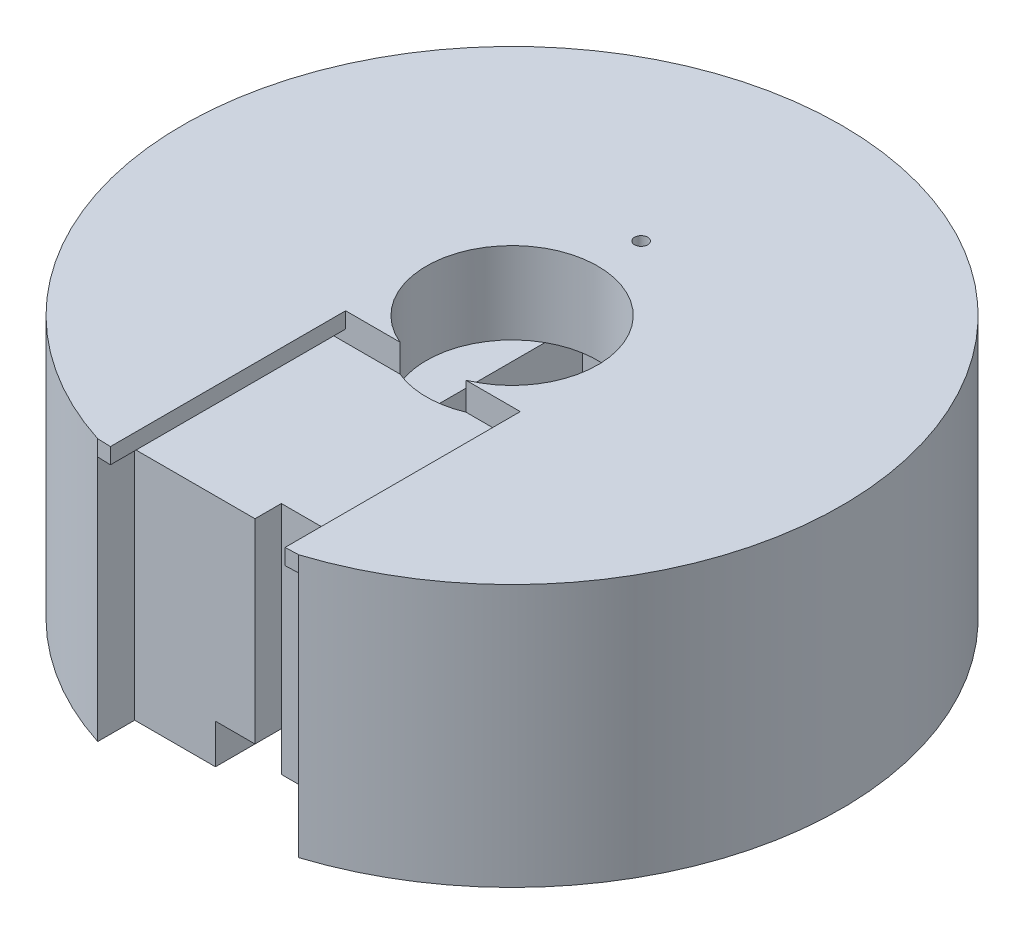
SolidWorks part; units mm, degrees
material "ABS"
ref_plane "Front Plane" through (0, 0, 0) normal (0, 0, 1) x (1, 0, 0)
ref_plane "Top Plane" through (0, 0, 0) normal (0, 1, 0) x (1, 0, 0)
ref_plane "Right Plane" through (0, 0, 0) normal (1, 0, 0) x (0, 0, -1)
ref_plane "Plane1" through (0, 0, -5.455) normal (0, 0, 1) x (1, 0, 0)
ref_axis "Axis1" through (0, 63.175, -5.455) along (0, -1, 0)
sketch "Sketch7" plane through (0, 0, 0) normal (0, 1, 0) x (1, 0, 0)
  line L0 (-6.35, 21.98) -> (-6.35, -11.07)
  line L1 (-5.95, 21.58) -> (5.95, 21.58) construction
  line L2 (-5.95, 21.58) -> (-5.95, -10.67) construction
  line L3 (-5.95, -10.67) -> (5.95, -10.67) construction
  line L4 (5.95, 21.58) -> (5.95, -10.67) construction
  line L5 (-5.95, 21.58) -> (5.95, -10.67) construction
  line L6 (-5.95, -10.67) -> (5.95, 21.58) construction
  line L7 (-6.35, -11.07) -> (6.35, -11.07)
  line L8 (6.35, 21.98) -> (6.35, -11.07)
  line L9 (-6.35, 21.98) -> (6.35, 21.98)
  circle A0 centre (0, 0) radius 50
  point P3 (0, 5.455)
  dimension "D1" = 100
  dimension "D2" = 11.9
  dimension "D3" = 32.25
  dimension "D4" = 0.4
extrude "Boss-Extrude4" add sketch "Sketch7" along normal blind 19.2
sketch "Sketch8" plane through (0, 19.2, 0) normal (0, 1, 0) x (1, 0, 0)
  line L0 (6.35, 21.98) -> (-6.35, 21.98) construction
  line L1 (-6.35, 17.055) -> (6.35, 17.055)
  line L2 (-6.35, 17.055) -> (-6.35, -6.145)
  line L3 (-6.35, -6.145) -> (6.35, -6.145)
  line L4 (6.35, 17.055) -> (6.35, -6.145)
  line L5 (-6.35, 17.055) -> (6.35, -6.145) construction
  line L6 (-6.35, -6.145) -> (6.35, 17.055) construction
  circle A0 centre (0, 0) radius 50
  circle A1 centre (0, 0) radius 50 construction
  point P0 (0, 5.455)
  dimension "D1" = 23.2
extrude "Boss-Extrude5" add sketch "Sketch8" along normal blind 8.2
sketch "Sketch11" plane through (0, 27.4, 0) normal (0, 1, 0) x (1, 0, 0)
  circle A0 centre (0, 0) radius 13
  circle A1 centre (0, 0) radius 50
  circle A2 centre (0, 0) radius 50 construction
  dimension "D1" = 26
extrude "Boss-Extrude6" add sketch "Sketch11" along normal blind 8.2
sketch "Sketch12" plane through (0, 19.2, 0) normal (0, -1, 0) x (1, 0, 0)
  line L0 (-6.35, 11.07) -> (6.35, 11.07) construction
  line L1 (6.35, -21.98) -> (-6.35, -21.98) construction
  circle A0 centre (0, 8.67) radius 1
  circle A1 centre (0, -19.58) radius 1
  dimension "D1" = 2.4
  dimension "D2" = 2
  dimension "D3" = 2.4
extrude "Cut-Extrude4" cut sketch "Sketch12" against normal through all
sketch "Sketch13" plane through (0, 0, 0) normal (0, -1, 0) x (1, 0, 0)
  line L1 (-15.25, 50) -> (15.25, 50)
  line L2 (-15.25, 50) -> (-15.25, 42)
  line L3 (-15.25, 42) -> (15.25, 42)
  line L4 (15.25, 50) -> (15.25, 42)
  circle A0 centre (0, 0) radius 50 construction
  point P6 (0, 42)
  dimension "D1" = 30.5
  dimension "D2" = 8
extrude "Cut-Extrude5" cut sketch "Sketch13" against normal up to surface (35.6 mm away) up to face at (0, 35.6, -20.58)
sketch "Sketch14" plane through (0, 0, 0) normal (0, -1, 0) x (1, 0, 0)
  line L0 (-6.35, 11.07) -> (6.35, 11.07) construction
  line L1 (-3, 11.07) -> (3, 11.07)
  line L2 (-3, 11.07) -> (-3, 42)
  line L3 (-3, 42) -> (3, 42)
  line L4 (3, 11.07) -> (3, 38)
  line L5 (-15.25, 42) -> (15.25, 42) construction
  line L6 (15.25, 42) -> (15.25, 47.6176) construction
  line L7 (3, 42) -> (15.25, 42)
  line L9 (3, 38) -> (15.25, 38)
  line L10 (15.25, 42) -> (15.25, 38)
  point P8 (0, 11.07)
  dimension "D1" = 6
  dimension "D2" = 0
  dimension "D3" = 4
extrude "Cut-Extrude6" cut sketch "Sketch14" against normal blind 6
sketch "Sketch15" plane through (0, 6, 0) normal (0, -1, 0) x (1, 0, 0)
  line L6 (15.25, 42) -> (3, 42)
  line L7 (15.25, 42) -> (15.25, 38)
  line L8 (15.25, 38) -> (3, 38)
  line L9 (3, 42) -> (3, 38)
extrude "Cut-Extrude7" cut sketch "Sketch15" against normal up to surface (29.6 mm away) up to face at (0, 35.6, 20.4044)
sketch "Sketch16" plane through (0, 35.6, 0) normal (0, 1, 0) x (1, 0, 0)
  line L2 (-15.25, -47.6176) -> (-15.25, -12)
  line L3 (-15.25, -12) -> (15.25, -12)
  line L4 (15.25, -47.6176) -> (15.25, -12)
  line L5 (15.25, -38) -> (15.25, -47.6176) construction
  arc A1 (15.25, -47.6176) -> (-15.25, -47.6176) centre (0, 0) ccw
  arc A2 (5, -12) -> (-5, -12) centre (0, 0) ccw
  circle A3 centre (0, 0) radius 13 construction
  line M8 (15.25, -38) -> (15.25, -47.6176)
  arc M9 (15.25, -47.6176) -> (-15.25, -47.6176) centre (0, 0) ccw
  line M10 (-15.25, -47.6176) -> (-15.25, -42)
  circle M12 centre (0, 19.58) radius 1
  circle M13 centre (0, 0) radius 13
  dimension "D1" = 12
extrude "Boss-Extrude11" add sketch "Sketch16" along normal blind 5.2 contours L4 L2 L3 M8 M9 M10 M13 M12 region at (0, 35.6, -48.6025)
sketch "Sketch20" plane through (0, 40.8, 0) normal (0, 1, 0) x (1, 0, 0)
  circle A0 centre (0, 0) radius 50
  arc A1 (15.25, -47.6176) -> (-15.25, -47.6176) centre (0, 0) ccw construction
extrude "Cut-Extrude8" cut sketch "Sketch20" against normal blind 1
sketch "Sketch21" plane through (0, 39.8, 0) normal (0, 1, 0) x (1, 0, 0)
  line L0 (-15.25, -12) -> (-13.25, -12)
  line L1 (-15.25, -12) -> (-5, -12) construction
  line L2 (-13.25, -12) -> (-13.25, -47.6856)
  line L3 (-13.25, -47.6856) -> (-15.25, -47.6176)
  line L4 (-15.25, -47.6176) -> (-15.25, -12)
  line L5 (0, -1008.67) -> (0, 48991.33) construction
  line L6 (13.25, -47.6856) -> (15.25, -47.6176)
  line L7 (13.25, -12) -> (13.25, -47.6856)
  line L8 (15.25, -12) -> (13.25, -12)
  line L9 (15.25, -47.6176) -> (15.25, -12)
  dimension "D1" = 2
extrude "Boss-Extrude12" add sketch "Sketch21" against normal offset from surface (2.4 mm away) 1.8 up to face at (0.75, 35.6, 26.125)
